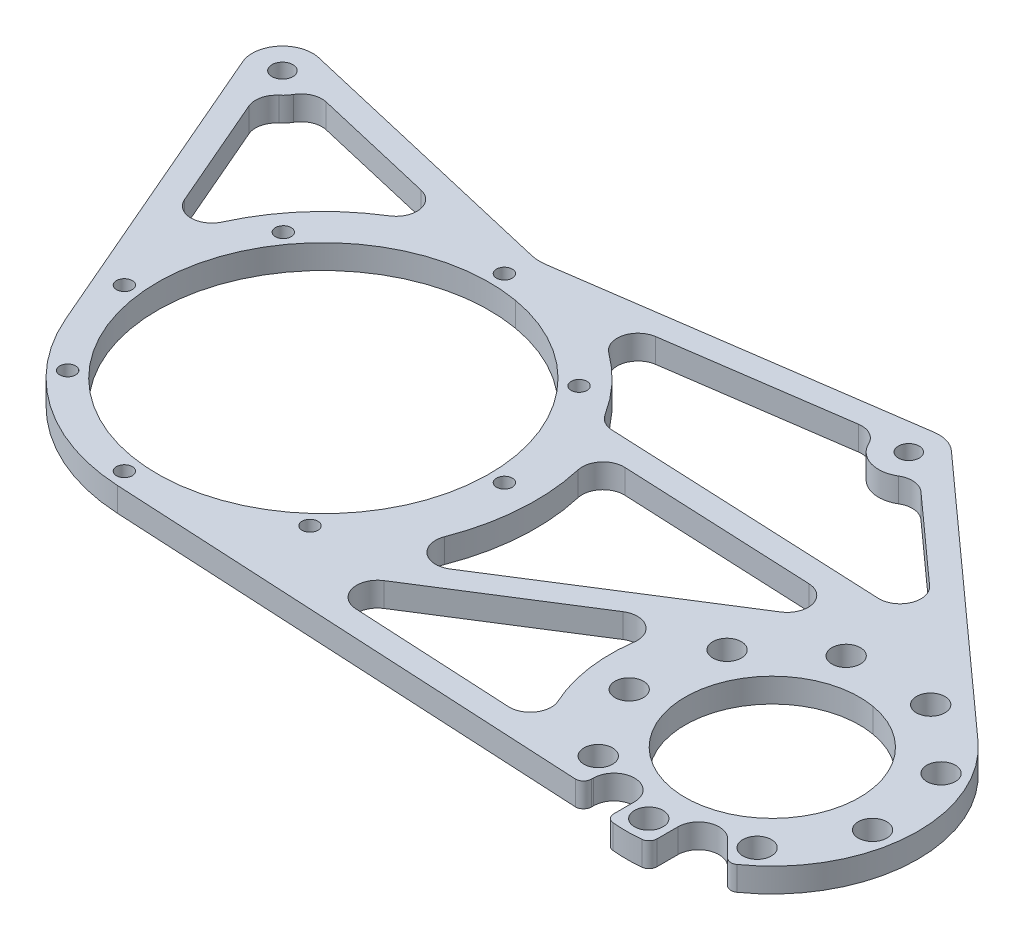
SolidWorks part; units mm, degrees
material "6061-T6 (SS)"
ref_plane "X-Y Datum" through (0, 0, 0) normal (0, 0, 1) x (1, 0, 0)
ref_plane "X-Z Datum" through (0, 0, 0) normal (0, 1, 0) x (1, 0, 0)
ref_plane "Y-Z Datum" through (0, 0, 0) normal (1, 0, 0) x (0, 0, -1)
sketch "Sketch2" plane through (0, 31.3819, 0) normal (0, 1, 0) x (1, 0, 0)
  line L0 (-693.7583, -176.702) -> (-693.7583, -183.2747) construction
  line L1 (-680.0808, -183.2747) -> (-680.0808, -176.702) construction
  line L2 (-668.9846, -172.1058) -> (-663.7197, -177.3707) construction
  line L3 (-693.7583, -176.702) -> (-693.7583, -183.2747)
  line L4 (-680.0808, -183.2747) -> (-680.0808, -176.702)
  line L5 (-668.9846, -172.1058) -> (-663.7197, -177.3707)
  line L6 (-966.641, -0.354) -> (-738.041, -0.354)
  line L7 (-727.7656, -5.5904) -> (-649.7224, -113.0358)
  line L9 (-977.8288, -19.0644) -> (-913.2312, -139.3061)
  line L10 (-706.7583, -177.279) -> (-706.7583, -176.702) construction
  line L11 (-706.7583, -177.279) -> (-706.7583, -176.702)
  line L12 (-861.9259, -171.8334) -> (-709.2983, -179.819)
  line L13 (-858.691, -110.0055) -> (-686.9195, -140.054) construction
  line L14 (-972.26, -24.9963) -> (-955.4664, -39.59) construction
  line L15 (-941.4162, -26.937) -> (-954.1775, -8.712) construction
  line L16 (-751.1929, -14.159) -> (-755.4346, -35.9995) construction
  line L17 (-737.4517, -41.8408) -> (-728.049, -21.6768) construction
  line L18 (-972.26, -24.9963) -> (-955.4664, -39.59)
  line L19 (-941.4162, -26.937) -> (-954.1775, -8.712)
  line L20 (-751.1929, -14.159) -> (-755.4346, -35.9995)
  line L21 (-737.4517, -41.8408) -> (-728.049, -21.6768)
  line L22 (-949.2186, -22.8753) -> (-746.0843, -28.2904)
  line L23 (-739.7146, -30.7335) -> (-656.1751, -105.8723)
  line L24 (-957.9647, -36.1729) -> (-915.5404, -134.527)
  arc A0 (-710.607, -179.4559) -> (-706.7583, -177.279) centre (-709.2983, -177.279) ccw construction
  arc A1 (-693.7583, -176.702) -> (-706.7583, -176.702) centre (-700.2583, -176.702) ccw construction
  arc A2 (-693.7583, -183.2747) -> (-691.4697, -185.8023) centre (-691.2183, -183.2747) ccw construction
  arc A3 (-691.4697, -185.8023) -> (-682.3694, -185.8023) centre (-686.9195, -140.054) ccw construction
  arc A4 (-682.3694, -185.8023) -> (-680.0808, -183.2747) centre (-682.6208, -183.2747) ccw construction
  arc A5 (-668.9846, -172.1058) -> (-680.0808, -176.702) centre (-673.5808, -176.702) ccw construction
  arc A6 (-663.7197, -177.3707) -> (-660.4619, -177.6519) centre (-661.9236, -175.5746) ccw construction
  arc A7 (-660.4619, -177.6519) -> (-710.607, -179.4559) centre (-686.9195, -140.054) ccw construction
  circle A8 centre (-858.691, -110.0055) radius 52.3875 construction
  circle A9 centre (-858.691, -110.0055) radius 61.9125 construction
  circle A10 centre (-738.041, -13.054) radius 12.7 construction
  circle A11 centre (-966.641, -13.054) radius 12.7 construction
  arc A12 (-710.607, -179.4559) -> (-706.7583, -177.279) centre (-709.2983, -177.279) ccw
  arc A13 (-693.7583, -176.702) -> (-706.7583, -176.702) centre (-700.2583, -176.702) ccw
  arc A14 (-693.7583, -183.2747) -> (-691.4697, -185.8023) centre (-691.2183, -183.2747) ccw
  arc A15 (-691.4697, -185.8023) -> (-682.3694, -185.8023) centre (-686.9195, -140.054) ccw
  arc A16 (-682.3694, -185.8023) -> (-680.0808, -183.2747) centre (-682.6208, -183.2747) ccw
  arc A17 (-668.9846, -172.1058) -> (-680.0808, -176.702) centre (-673.5808, -176.702) ccw
  arc A18 (-663.7197, -177.3707) -> (-660.4619, -177.6519) centre (-661.9236, -175.5746) ccw
  arc A19 (-660.4619, -177.6519) -> (-710.607, -179.4559) centre (-686.9195, -140.054) ccw
  circle A20 centre (-858.691, -110.0055) radius 52.3875
  circle A21 centre (-858.691, -110.0055) radius 61.9125
  circle A22 centre (-738.041, -13.054) radius 12.7
  circle A23 centre (-966.641, -13.054) radius 12.7
  circle A24 centre (-901.1618, -148.2463) radius 2.5 construction
  circle A25 centre (-915.528, -115.9793) radius 2.5 construction
  circle A26 centre (-904.9264, -76.4135) radius 2.5 construction
  circle A27 centre (-858.691, -52.8555) radius 2.5 construction
  circle A28 centre (-816.2203, -71.7646) radius 2.5 construction
  circle A29 centre (-801.541, -110.0055) radius 2.5 construction
  circle A30 centre (-820.4502, -152.4762) radius 2.5 construction
  circle A31 centre (-864.6648, -166.8424) radius 2.5 construction
  circle A32 centre (-901.1618, -148.2463) radius 2.5
  circle A33 centre (-915.528, -115.9793) radius 2.5
  circle A34 centre (-904.9264, -76.4135) radius 2.5
  circle A35 centre (-858.691, -52.8555) radius 2.5
  circle A36 centre (-816.2203, -71.7646) radius 2.5
  circle A37 centre (-801.541, -110.0055) radius 2.5
  circle A38 centre (-820.4502, -152.4762) radius 2.5
  circle A39 centre (-864.6648, -166.8424) radius 2.5
  circle A40 centre (-686.9195, -140.054) radius 27.4955 construction
  circle A41 centre (-686.9195, -140.054) radius 27.4955
  circle A42 centre (-711.9883, -169.9297) radius 4.5 construction
  circle A43 centre (-725.3271, -146.8263) radius 4.5 construction
  circle A44 centre (-720.6945, -120.554) radius 4.5 construction
  circle A45 centre (-700.2583, -103.406) radius 4.5 construction
  circle A46 centre (-673.5808, -103.406) radius 4.5 construction
  circle A47 centre (-653.1446, -120.554) radius 4.5 construction
  circle A48 centre (-648.512, -146.8263) radius 4.5 construction
  circle A49 centre (-661.8508, -169.9297) radius 4.5 construction
  circle A50 centre (-686.9195, -179.054) radius 4.5 construction
  circle A51 centre (-711.9883, -169.9297) radius 4.5
  circle A52 centre (-725.3271, -146.8263) radius 4.5
  circle A53 centre (-720.6945, -120.554) radius 4.5
  circle A54 centre (-700.2583, -103.406) radius 4.5
  circle A55 centre (-673.5808, -103.406) radius 4.5
  circle A56 centre (-653.1446, -120.554) radius 4.5
  circle A57 centre (-648.512, -146.8263) radius 4.5
  circle A58 centre (-661.8508, -169.9297) radius 4.5
  circle A59 centre (-686.9195, -179.054) radius 4.5
  circle A60 centre (-966.641, -13.054) radius 3.3
  circle A61 centre (-738.041, -13.054) radius 3.3
  arc A62 (-955.4664, -39.59) -> (-941.4162, -26.937) centre (-949.2186, -32.4003) ccw construction
  arc A63 (-749.3237, -37.1863) -> (-742.8448, -38.4445) centre (-746.0843, -37.8154) ccw construction
  arc A64 (-742.8448, -38.4445) -> (-749.3237, -37.1863) centre (-746.0843, -37.8154) ccw construction
  arc A65 (-755.4346, -35.9995) -> (-737.4517, -41.8408) centre (-746.0843, -37.8154) ccw construction
  arc A66 (-955.4664, -39.59) -> (-941.4162, -26.937) centre (-949.2186, -32.4003) ccw
  arc A67 (-749.3237, -37.1863) -> (-742.8448, -38.4445) centre (-746.0843, -37.8154) ccw
  arc A68 (-742.8448, -38.4445) -> (-749.3237, -37.1863) centre (-746.0843, -37.8154) ccw
  arc A69 (-755.4346, -35.9995) -> (-737.4517, -41.8408) centre (-746.0843, -37.8154) ccw
  circle A70 centre (-949.2186, -32.4003) radius 3.3
  circle A71 centre (-949.2186, -32.4003) radius 9.525
  circle A72 centre (-746.0843, -37.8154) radius 9.525
  point P94 (-949.2186, -32.4003)
  dimension "D1" = 6.6
  dimension "D2" = 6.6
  dimension "D3" = 6.6
extrude "Boss-Extrude1" add sketch "Sketch2" along normal blind 7.62 contours A21 A39 A38 A37 A36 A35 A34 A33 A32 A20 | A18 A19 A12 L11 A13 L3 A14 A15 A16 L4 A17 L5 A59 A58 A57 A56 A55 A54 A53 A52 A51 A41 | L13 A21 L12 A12 A19 | A21 L13 A19 L23 L21 A69 L20 L22 L19 A66 L18 L24 | A69 A72 A68 A67 | A72 L22 L20 | A72 L21 L23 | A71 L24 L18 | A71 L19 L22 | A71 A66 L22 A70 region at (-700.2583, 31.3819, 168.9016) region at (-773.051, 31.3819, 154.3682) region at (-890.9045, 31.3819, 160.8157) region at (-806.8861, 31.3819, 67.2042) region at (-956.9478, 31.3819, 38.0512) region at (-736.2382, 31.3819, 35.8095) region at (-956.6903, 31.3819, 37.8629) region at (-748.9437, 31.3819, 46.6182) region at (-752.4763, 31.3819, 29.8585) region at (-944.5842, 31.3819, 23.8004)
sketch "Sketch3" plane through (0, 31.3819, 0) normal (0, -1, 0) x (1, 0, 0)
  line L1 (-949.2186, 22.8753) -> (-746.0843, 28.2904) construction
  line L5 (-861.9259, 171.8334) -> (-709.2983, 179.819) construction
  line L6 (-977.8288, 19.0644) -> (-913.2312, 139.3061) construction
  line L7 (-727.7656, 5.5904) -> (-649.7224, 113.0358) construction
  line L13 (-751.1929, 14.159) -> (-755.4346, 35.9995) construction
  line L16 (-966.641, 0.354) -> (-738.041, 0.354) construction
  line L19 (-663.7197, 177.3707) -> (-668.9846, 172.1058)
  line L20 (-680.0808, 176.702) -> (-680.0808, 183.2747)
  line L21 (-693.7583, 183.2747) -> (-693.7583, 176.702)
  line L22 (-706.7583, 176.702) -> (-706.7583, 177.279)
  line L23 (-663.7197, 177.3707) -> (-668.9846, 172.1058)
  line L24 (-680.0808, 176.702) -> (-680.0808, 183.2747)
  line L25 (-693.7583, 183.2747) -> (-693.7583, 176.702)
  line L26 (-706.7583, 176.702) -> (-706.7583, 177.279)
  line L28 (-861.9259, 171.8334) -> (-709.2983, 179.819)
  line L29 (-977.8288, 19.0644) -> (-913.2312, 139.3061)
  line L30 (-727.7656, 5.5904) -> (-649.7224, 113.0358)
  line L31 (-966.641, 0.354) -> (-738.041, 0.354)
  line L34 (-737.4517, 41.8408) -> (-728.049, 21.6768) construction
  line L35 (-972.26, 24.9963) -> (-955.4664, 39.59) construction
  line L36 (-947.0539, 23.1246) -> (-856.9722, 44.1471)
  line L37 (-856.9722, 44.1471) -> (-747.4408, 28.3875)
  line L44 (-941.4162, 26.937) -> (-954.1775, 8.712) construction
  line L45 (-957.9647, 36.1729) -> (-915.5404, 134.527) construction
  line L46 (-739.7146, 30.7335) -> (-656.1751, 105.8723) construction
  line L47 (-861.9259, 171.8334) -> (-709.2983, 179.819)
  line L48 (-977.8288, 19.0644) -> (-913.2312, 139.3061)
  line L49 (-727.7656, 5.5904) -> (-649.7224, 113.0358)
  line L50 (-966.641, 0.354) -> (-738.041, 0.354)
  line L51 (-949.2186, 22.8753) -> (-746.0843, 28.2904)
  line L52 (-751.1929, 14.159) -> (-755.4346, 35.9995)
  line L53 (-737.4517, 41.8408) -> (-728.049, 21.6768)
  line L54 (-972.26, 24.9963) -> (-955.4664, 39.59)
  line L55 (-941.4162, 26.937) -> (-954.1775, 8.712)
  line L56 (-957.9647, 36.1729) -> (-915.5404, 134.527)
  line L57 (-739.7146, 30.7335) -> (-656.1751, 105.8723)
  arc A1 (-737.4517, 41.8408) -> (-755.4346, 35.9995) centre (-746.0843, 37.8154) ccw construction
  circle A3 centre (-966.641, 13.054) radius 12.7
  circle A5 centre (-966.641, 13.054) radius 12.7
  circle A7 centre (-738.041, 13.054) radius 12.7
  circle A9 centre (-738.041, 13.054) radius 12.7
  circle A11 centre (-858.691, 110.0055) radius 61.9125
  circle A13 centre (-858.691, 110.0055) radius 61.9125
  circle A15 centre (-858.691, 110.0055) radius 52.3875
  circle A17 centre (-858.691, 110.0055) radius 52.3875
  circle A19 centre (-686.9195, 140.054) radius 27.4955
  circle A21 centre (-686.9195, 140.054) radius 27.4955
  circle A23 centre (-864.6648, 166.8424) radius 2.5
  circle A25 centre (-864.6648, 166.8424) radius 2.5
  circle A27 centre (-820.4502, 152.4762) radius 2.5
  circle A29 centre (-820.4502, 152.4762) radius 2.5
  circle A31 centre (-801.541, 110.0055) radius 2.5
  circle A33 centre (-801.541, 110.0055) radius 2.5
  circle A35 centre (-816.2203, 71.7646) radius 2.5
  circle A37 centre (-816.2203, 71.7646) radius 2.5
  circle A39 centre (-858.691, 52.8555) radius 2.5
  circle A41 centre (-858.691, 52.8555) radius 2.5
  circle A43 centre (-904.9264, 76.4135) radius 2.5
  circle A46 centre (-904.9264, 76.4135) radius 2.5
  circle A47 centre (-915.528, 115.9793) radius 2.5
  circle A48 centre (-915.528, 115.9793) radius 2.5
  circle A49 centre (-901.1618, 148.2463) radius 2.5
  circle A50 centre (-901.1618, 148.2463) radius 2.5
  circle A51 centre (-720.6945, 120.554) radius 4.5
  circle A52 centre (-720.6945, 120.554) radius 4.5
  circle A68 centre (-725.3271, 146.8263) radius 4.5
  circle A69 centre (-725.3271, 146.8263) radius 4.5
  circle A70 centre (-711.9883, 169.9297) radius 4.5
  circle A71 centre (-711.9883, 169.9297) radius 4.5
  circle A72 centre (-738.041, 13.054) radius 3.3
  circle A73 centre (-738.041, 13.054) radius 3.3
  circle A74 centre (-966.641, 13.054) radius 3.3
  circle A75 centre (-966.641, 13.054) radius 3.3
  circle A76 centre (-686.9195, 179.054) radius 4.5
  circle A77 centre (-686.9195, 179.054) radius 4.5
  circle A78 centre (-661.8508, 169.9297) radius 4.5
  circle A79 centre (-661.8508, 169.9297) radius 4.5
  circle A80 centre (-648.512, 146.8263) radius 4.5
  circle A81 centre (-648.512, 146.8263) radius 4.5
  circle A82 centre (-653.1446, 120.554) radius 4.5
  circle A83 centre (-653.1446, 120.554) radius 4.5
  circle A84 centre (-673.5808, 103.406) radius 4.5
  circle A85 centre (-673.5808, 103.406) radius 4.5
  circle A86 centre (-700.2583, 103.406) radius 4.5
  circle A87 centre (-700.2583, 103.406) radius 4.5
  arc A95 (-710.607, 179.4559) -> (-660.4619, 177.6519) centre (-686.9195, 140.054) ccw
  arc A96 (-660.4619, 177.6519) -> (-663.7197, 177.3707) centre (-661.9236, 175.5746) ccw
  arc A97 (-680.0808, 176.702) -> (-668.9846, 172.1058) centre (-673.5808, 176.702) ccw
  arc A98 (-680.0808, 183.2747) -> (-682.3694, 185.8023) centre (-682.6208, 183.2747) ccw
  arc A99 (-682.3694, 185.8023) -> (-691.4697, 185.8023) centre (-686.9195, 140.054) ccw
  arc A100 (-691.4697, 185.8023) -> (-693.7583, 183.2747) centre (-691.2183, 183.2747) ccw
  arc A101 (-706.7583, 176.702) -> (-693.7583, 176.702) centre (-700.2583, 176.702) ccw
  arc A102 (-706.7583, 177.279) -> (-710.607, 179.4559) centre (-709.2983, 177.279) ccw
  arc A103 (-710.607, 179.4559) -> (-660.4619, 177.6519) centre (-686.9195, 140.054) ccw
  arc A104 (-660.4619, 177.6519) -> (-663.7197, 177.3707) centre (-661.9236, 175.5746) ccw
  arc A105 (-680.0808, 176.702) -> (-668.9846, 172.1058) centre (-673.5808, 176.702) ccw
  arc A106 (-680.0808, 183.2747) -> (-682.3694, 185.8023) centre (-682.6208, 183.2747) ccw
  arc A107 (-682.3694, 185.8023) -> (-691.4697, 185.8023) centre (-686.9195, 140.054) ccw
  arc A108 (-691.4697, 185.8023) -> (-693.7583, 183.2747) centre (-691.2183, 183.2747) ccw
  arc A109 (-706.7583, 176.702) -> (-693.7583, 176.702) centre (-700.2583, 176.702) ccw
  arc A110 (-706.7583, 177.279) -> (-710.607, 179.4559) centre (-709.2983, 177.279) ccw
  circle A152 centre (-746.0843, 37.8154) radius 9.525
  circle A153 centre (-746.0843, 37.8154) radius 9.525
  circle A154 centre (-949.2186, 32.4003) radius 9.525
  circle A155 centre (-949.2186, 32.4003) radius 9.525
  circle A156 centre (-949.2186, 32.4003) radius 3.3
  circle A157 centre (-949.2186, 32.4003) radius 3.3
  arc A158 (-941.4162, 26.937) -> (-955.4664, 39.59) centre (-949.2186, 32.4003) ccw construction
  arc A159 (-742.8448, 38.4445) -> (-749.3237, 37.1863) centre (-746.0843, 37.8154) ccw
  arc A160 (-749.3237, 37.1863) -> (-742.8448, 38.4445) centre (-746.0843, 37.8154) ccw
  arc A161 (-742.8448, 38.4445) -> (-749.3237, 37.1863) centre (-746.0843, 37.8154) ccw
  arc A162 (-749.3237, 37.1863) -> (-742.8448, 38.4445) centre (-746.0843, 37.8154) ccw
  arc A163 (-737.4517, 41.8408) -> (-755.4346, 35.9995) centre (-746.0843, 37.8154) ccw
  arc A164 (-941.4162, 26.937) -> (-955.4664, 39.59) centre (-949.2186, 32.4003) ccw
  dimension "D24" = 0
  dimension "D25" = 0
  dimension "D26" = 90.0818
  dimension "D27" = 21.0225
  dimension "D1" = 0
  dimension "D2" = 0
  dimension "D3" = 0
  dimension "D4" = 0
  dimension "D5" = 0
  dimension "D6" = 0
  dimension "D7" = 0
  dimension "D8" = 0
  dimension "D9" = 0
  dimension "D10" = 0
  dimension "D11" = 0
  dimension "D12" = 0
  dimension "D13" = 0
  dimension "D14" = 0
  dimension "D15" = 0
  dimension "D16" = 0
  dimension "D17" = 0
  dimension "D18" = 0
  dimension "D19" = 0
  dimension "D20" = 0
  dimension "D21" = 0
  dimension "D22" = 0
  dimension "D23" = 0
  dimension "D52" = 0
  dimension "D53" = 0
  dimension "D54" = 0
  dimension "D55" = 0
ref_point "Point1"
ref_point "Point2"
ref_plane "Plane1" through (-858.691, 31.3819, 110.0055) normal (0.985, 0, 0.1723) x (0.1723, 0, -0.985)
ref_plane "Plane2" through (-686.9195, 31.3819, 140.054) normal (-0.985, 0, -0.1723) x (-0.1723, 0, 0.985)
split line "Split Line1"
split line "Split Line2"
ref_axis "Axis1" through (-858.691, 39.0019, 110.0055) along (0, -1, 0)
ref_axis "Axis2" through (-686.9195, 39.0019, 140.054) along (0, -1, 0)
extrude "Cut-Extrude1" cut sketch "Sketch3" against normal through all contours L36 L55 L51 L52 L37 | A155 L51 L55 L36 | A153 L37 L52 L51 region at (-751.5495, 31.3819, 28.5688) region at (-850.6911, 31.3819, 31.7926) region at (-945.2616, 31.3819, 23.2848)
fillet "Fillet2" radius 12.7 1 edges at (-856.9722, 35.1919, 44.1471)
sketch "Sketch4" plane through (0, 31.3819, 0) normal (0, -1, 0) x (1, 0, 0)
  line L0 (-861.9259, 171.8334) -> (-709.2983, 179.819) construction
  line L1 (-727.7656, 5.5904) -> (-649.7224, 113.0358) construction
  line L2 (-977.8288, 19.0644) -> (-913.2312, 139.3061) construction
  line L4 (-706.7583, 176.702) -> (-706.7583, 177.279)
  line L5 (-663.7197, 177.3707) -> (-668.9846, 172.1058)
  line L6 (-680.0808, 176.702) -> (-680.0808, 183.2747)
  line L7 (-693.7583, 183.2747) -> (-693.7583, 176.702)
  line L8 (-706.7583, 176.702) -> (-706.7583, 177.279)
  line L9 (-663.7197, 177.3707) -> (-668.9846, 172.1058)
  line L10 (-680.0808, 176.702) -> (-680.0808, 183.2747)
  line L11 (-693.7583, 183.2747) -> (-693.7583, 176.702)
  line L13 (-966.641, 0.354) -> (-738.041, 0.354) construction
  line L14 (-861.9259, 171.8334) -> (-709.2983, 179.819)
  line L15 (-727.7656, 5.5904) -> (-649.7224, 113.0358)
  line L16 (-977.8288, 19.0644) -> (-913.2312, 139.3061)
  line L17 (-861.9259, 171.8334) -> (-709.2983, 179.819) construction
  line L19 (-966.641, 0.354) -> (-738.041, 0.354)
  line L20 (-922.3006, 99.6155) -> (-952.4637, 29.6868)
  line L21 (-952.4637, 29.6868) -> (-875.2298, 47.711)
  line L22 (-727.338, 171.2447) -> (-811.2904, 166.8523)
  line L23 (-811.2904, 166.8523) -> (-732.4764, 117.0088)
  line L24 (-812.7344, 158.7495) -> (-704.8294, 90.5083)
  line L25 (-704.8294, 90.5083) -> (-795.9976, 86.3933)
  line L26 (-837.6883, 49.071) -> (-755.593, 37.2589)
  line L27 (-802.4787, 78.4731) -> (-692.5141, 83.4364)
  line L28 (-692.5141, 83.4364) -> (-737.8716, 42.64)
  line L29 (-977.8288, 19.0644) -> (-913.2312, 139.3061) construction
  line L30 (-727.7656, 5.5904) -> (-649.7224, 113.0358) construction
  line L31 (-966.641, 0.354) -> (-738.041, 0.354) construction
  line L32 (-663.7197, 177.3707) -> (-668.9846, 172.1058)
  line L33 (-680.0808, 176.702) -> (-680.0808, 183.2747)
  line L34 (-693.7583, 183.2747) -> (-693.7583, 176.702)
  line L35 (-706.7583, 176.702) -> (-706.7583, 177.279)
  line L36 (-663.7197, 177.3707) -> (-668.9846, 172.1058)
  line L37 (-680.0808, 176.702) -> (-680.0808, 183.2747)
  line L38 (-693.7583, 183.2747) -> (-693.7583, 176.702)
  line L39 (-706.7583, 176.702) -> (-706.7583, 177.279)
  line L40 (-949.2186, 22.8753) -> (-746.0843, 28.2904) construction
  line L41 (-751.1929, 14.159) -> (-755.4346, 35.9995) construction
  line L42 (-737.4517, 41.8408) -> (-728.049, 21.6768) construction
  line L43 (-972.26, 24.9963) -> (-955.4664, 39.59) construction
  line L44 (-941.4162, 26.937) -> (-954.1775, 8.712) construction
  line L45 (-957.9647, 36.1729) -> (-915.5404, 134.527) construction
  line L46 (-739.7146, 30.7335) -> (-656.1751, 105.8723) construction
  line L47 (-861.9259, 171.8334) -> (-709.2983, 179.819)
  line L48 (-977.8288, 19.0644) -> (-913.2312, 139.3061)
  line L49 (-727.7656, 5.5904) -> (-649.7224, 113.0358)
  line L50 (-966.641, 0.354) -> (-738.041, 0.354)
  line L51 (-949.2186, 22.8753) -> (-746.0843, 28.2904)
  line L52 (-751.1929, 14.159) -> (-755.4346, 35.9995)
  line L53 (-737.4517, 41.8408) -> (-728.049, 21.6768)
  line L54 (-972.26, 24.9963) -> (-955.4664, 39.59)
  line L55 (-941.4162, 26.937) -> (-954.1775, 8.712)
  line L56 (-957.9647, 36.1729) -> (-915.5404, 134.527)
  line L57 (-739.7146, 30.7335) -> (-656.1751, 105.8723)
  line L58 (-947.0539, 23.1246) -> (-859.3005, 43.6037) construction
  line L60 (-854.6056, 43.8066) -> (-747.4408, 28.3875) construction
  circle A1 centre (-858.691, 110.0055) radius 52.3875
  circle A2 centre (-858.691, 110.0055) radius 52.3875
  circle A3 centre (-858.691, 110.0055) radius 61.9125
  circle A4 centre (-858.691, 110.0055) radius 61.9125
  circle A5 centre (-738.041, 13.054) radius 12.7
  circle A6 centre (-738.041, 13.054) radius 12.7
  circle A7 centre (-966.641, 13.054) radius 12.7
  circle A8 centre (-966.641, 13.054) radius 12.7
  circle A9 centre (-858.691, 52.8555) radius 2.5
  circle A10 centre (-858.691, 52.8555) radius 2.5
  circle A11 centre (-816.2203, 71.7646) radius 2.5
  circle A12 centre (-816.2203, 71.7646) radius 2.5
  circle A13 centre (-801.541, 110.0055) radius 2.5
  circle A14 centre (-801.541, 110.0055) radius 2.5
  circle A15 centre (-820.4502, 152.4762) radius 2.5
  circle A16 centre (-820.4502, 152.4762) radius 2.5
  circle A17 centre (-864.6648, 166.8424) radius 2.5
  circle A18 centre (-864.6648, 166.8424) radius 2.5
  circle A19 centre (-686.9195, 140.054) radius 27.4955
  circle A20 centre (-686.9195, 140.054) radius 27.4955
  circle A21 centre (-725.3271, 146.8263) radius 4.5
  circle A22 centre (-725.3271, 146.8263) radius 4.5
  circle A23 centre (-720.6945, 120.554) radius 4.5
  circle A24 centre (-720.6945, 120.554) radius 4.5
  circle A25 centre (-901.1618, 148.2463) radius 2.5
  circle A26 centre (-901.1618, 148.2463) radius 2.5
  circle A27 centre (-915.528, 115.9793) radius 2.5
  circle A28 centre (-915.528, 115.9793) radius 2.5
  circle A29 centre (-904.9264, 76.4135) radius 2.5
  circle A30 centre (-904.9264, 76.4135) radius 2.5
  circle A31 centre (-661.8508, 169.9297) radius 4.5
  circle A32 centre (-661.8508, 169.9297) radius 4.5
  circle A33 centre (-686.9195, 179.054) radius 4.5
  circle A34 centre (-686.9195, 179.054) radius 4.5
  circle A35 centre (-966.641, 13.054) radius 3.3
  circle A36 centre (-966.641, 13.054) radius 3.3
  circle A37 centre (-738.041, 13.054) radius 3.3
  circle A38 centre (-738.041, 13.054) radius 3.3
  circle A39 centre (-711.9883, 169.9297) radius 4.5
  circle A40 centre (-711.9883, 169.9297) radius 4.5
  circle A41 centre (-700.2583, 103.406) radius 4.5
  circle A42 centre (-700.2583, 103.406) radius 4.5
  circle A43 centre (-673.5808, 103.406) radius 4.5
  circle A44 centre (-673.5808, 103.406) radius 4.5
  circle A45 centre (-653.1446, 120.554) radius 4.5
  circle A46 centre (-653.1446, 120.554) radius 4.5
  circle A47 centre (-648.512, 146.8263) radius 4.5
  circle A48 centre (-648.512, 146.8263) radius 4.5
  arc A49 (-875.2298, 47.711) -> (-922.3006, 99.6155) centre (-858.691, 110.0055) cw
  arc A50 (-727.338, 171.2447) -> (-732.4764, 117.0088) centre (-686.9195, 140.054) ccw
  arc A51 (-812.7344, 158.7495) -> (-795.9976, 86.3933) centre (-858.691, 110.0055) cw
  arc A52 (-837.6883, 49.071) -> (-802.4787, 78.4731) centre (-858.691, 110.0055) ccw
  arc A53 (-737.4517, 41.8408) -> (-755.4346, 35.9995) centre (-746.0843, 37.8154) ccw construction
  circle A54 centre (-966.641, 13.054) radius 12.7
  circle A55 centre (-966.641, 13.054) radius 12.7
  arc A56 (-706.7583, 177.279) -> (-710.607, 179.4559) centre (-709.2983, 177.279) ccw
  arc A57 (-710.607, 179.4559) -> (-660.4619, 177.6519) centre (-686.9195, 140.054) ccw
  arc A58 (-660.4619, 177.6519) -> (-663.7197, 177.3707) centre (-661.9236, 175.5746) ccw
  arc A59 (-680.0808, 176.702) -> (-668.9846, 172.1058) centre (-673.5808, 176.702) ccw
  arc A60 (-680.0808, 183.2747) -> (-682.3694, 185.8023) centre (-682.6208, 183.2747) ccw
  arc A61 (-682.3694, 185.8023) -> (-691.4697, 185.8023) centre (-686.9195, 140.054) ccw
  arc A62 (-691.4697, 185.8023) -> (-693.7583, 183.2747) centre (-691.2183, 183.2747) ccw
  arc A63 (-706.7583, 176.702) -> (-693.7583, 176.702) centre (-700.2583, 176.702) ccw
  arc A64 (-706.7583, 177.279) -> (-710.607, 179.4559) centre (-709.2983, 177.279) ccw
  arc A65 (-710.607, 179.4559) -> (-660.4619, 177.6519) centre (-686.9195, 140.054) ccw
  arc A66 (-660.4619, 177.6519) -> (-663.7197, 177.3707) centre (-661.9236, 175.5746) ccw
  arc A67 (-680.0808, 176.702) -> (-668.9846, 172.1058) centre (-673.5808, 176.702) ccw
  arc A68 (-680.0808, 183.2747) -> (-682.3694, 185.8023) centre (-682.6208, 183.2747) ccw
  arc A69 (-682.3694, 185.8023) -> (-691.4697, 185.8023) centre (-686.9195, 140.054) ccw
  arc A70 (-691.4697, 185.8023) -> (-693.7583, 183.2747) centre (-691.2183, 183.2747) ccw
  arc A71 (-706.7583, 176.702) -> (-693.7583, 176.702) centre (-700.2583, 176.702) ccw
  circle A72 centre (-738.041, 13.054) radius 12.7
  circle A73 centre (-738.041, 13.054) radius 12.7
  circle A74 centre (-858.691, 110.0055) radius 61.9125
  circle A75 centre (-858.691, 110.0055) radius 61.9125
  circle A76 centre (-858.691, 110.0055) radius 52.3875
  circle A77 centre (-858.691, 110.0055) radius 52.3875
  circle A78 centre (-686.9195, 140.054) radius 27.4955
  circle A79 centre (-686.9195, 140.054) radius 27.4955
  circle A80 centre (-864.6648, 166.8424) radius 2.5
  circle A81 centre (-864.6648, 166.8424) radius 2.5
  circle A82 centre (-820.4502, 152.4762) radius 2.5
  circle A83 centre (-820.4502, 152.4762) radius 2.5
  circle A84 centre (-801.541, 110.0055) radius 2.5
  circle A85 centre (-801.541, 110.0055) radius 2.5
  circle A86 centre (-816.2203, 71.7646) radius 2.5
  circle A87 centre (-816.2203, 71.7646) radius 2.5
  circle A88 centre (-858.691, 52.8555) radius 2.5
  circle A89 centre (-858.691, 52.8555) radius 2.5
  circle A90 centre (-904.9264, 76.4135) radius 2.5
  circle A91 centre (-904.9264, 76.4135) radius 2.5
  circle A92 centre (-915.528, 115.9793) radius 2.5
  circle A93 centre (-915.528, 115.9793) radius 2.5
  circle A94 centre (-901.1618, 148.2463) radius 2.5
  circle A95 centre (-901.1618, 148.2463) radius 2.5
  circle A96 centre (-720.6945, 120.554) radius 4.5
  circle A97 centre (-720.6945, 120.554) radius 4.5
  circle A98 centre (-725.3271, 146.8263) radius 4.5
  circle A99 centre (-725.3271, 146.8263) radius 4.5
  circle A100 centre (-711.9883, 169.9297) radius 4.5
  circle A101 centre (-711.9883, 169.9297) radius 4.5
  circle A102 centre (-738.041, 13.054) radius 3.3
  circle A103 centre (-738.041, 13.054) radius 3.3
  circle A104 centre (-966.641, 13.054) radius 3.3
  circle A105 centre (-966.641, 13.054) radius 3.3
  circle A106 centre (-686.9195, 179.054) radius 4.5
  circle A107 centre (-686.9195, 179.054) radius 4.5
  circle A108 centre (-661.8508, 169.9297) radius 4.5
  circle A109 centre (-661.8508, 169.9297) radius 4.5
  circle A110 centre (-648.512, 146.8263) radius 4.5
  circle A111 centre (-648.512, 146.8263) radius 4.5
  circle A112 centre (-653.1446, 120.554) radius 4.5
  circle A113 centre (-653.1446, 120.554) radius 4.5
  circle A114 centre (-673.5808, 103.406) radius 4.5
  circle A115 centre (-673.5808, 103.406) radius 4.5
  circle A116 centre (-700.2583, 103.406) radius 4.5
  circle A117 centre (-700.2583, 103.406) radius 4.5
  circle A118 centre (-746.0843, 37.8154) radius 9.525
  circle A119 centre (-746.0843, 37.8154) radius 9.525
  circle A120 centre (-949.2186, 32.4003) radius 9.525
  circle A121 centre (-949.2186, 32.4003) radius 9.525
  circle A122 centre (-949.2186, 32.4003) radius 3.3
  circle A123 centre (-949.2186, 32.4003) radius 3.3
  arc A124 (-941.4162, 26.937) -> (-955.4664, 39.59) centre (-949.2186, 32.4003) ccw construction
  arc A125 (-742.8448, 38.4445) -> (-749.3237, 37.1863) centre (-746.0843, 37.8154) ccw
  arc A126 (-749.3237, 37.1863) -> (-742.8448, 38.4445) centre (-746.0843, 37.8154) ccw
  arc A127 (-742.8448, 38.4445) -> (-749.3237, 37.1863) centre (-746.0843, 37.8154) ccw
  arc A128 (-749.3237, 37.1863) -> (-742.8448, 38.4445) centre (-746.0843, 37.8154) ccw
  arc A129 (-737.4517, 41.8408) -> (-755.4346, 35.9995) centre (-746.0843, 37.8154) ccw
  arc A130 (-941.4162, 26.937) -> (-955.4664, 39.59) centre (-949.2186, 32.4003) ccw
  arc A135 (-710.607, 179.4559) -> (-660.4619, 177.6519) centre (-686.9195, 140.054) ccw
  arc A136 (-660.4619, 177.6519) -> (-663.7197, 177.3707) centre (-661.9236, 175.5746) ccw
  arc A137 (-680.0808, 176.702) -> (-668.9846, 172.1058) centre (-673.5808, 176.702) ccw
  arc A138 (-680.0808, 183.2747) -> (-682.3694, 185.8023) centre (-682.6208, 183.2747) ccw
  arc A139 (-682.3694, 185.8023) -> (-691.4697, 185.8023) centre (-686.9195, 140.054) ccw
  arc A140 (-691.4697, 185.8023) -> (-693.7583, 183.2747) centre (-691.2183, 183.2747) ccw
  arc A141 (-706.7583, 176.702) -> (-693.7583, 176.702) centre (-700.2583, 176.702) ccw
  arc A142 (-706.7583, 177.279) -> (-710.607, 179.4559) centre (-709.2983, 177.279) ccw
  arc A143 (-710.607, 179.4559) -> (-660.4619, 177.6519) centre (-686.9195, 140.054) ccw
  arc A144 (-660.4619, 177.6519) -> (-663.7197, 177.3707) centre (-661.9236, 175.5746) ccw
  arc A145 (-680.0808, 176.702) -> (-668.9846, 172.1058) centre (-673.5808, 176.702) ccw
  arc A146 (-680.0808, 183.2747) -> (-682.3694, 185.8023) centre (-682.6208, 183.2747) ccw
  arc A147 (-682.3694, 185.8023) -> (-691.4697, 185.8023) centre (-686.9195, 140.054) ccw
  arc A148 (-691.4697, 185.8023) -> (-693.7583, 183.2747) centre (-691.2183, 183.2747) ccw
  arc A149 (-706.7583, 176.702) -> (-693.7583, 176.702) centre (-700.2583, 176.702) ccw
  arc A150 (-706.7583, 177.279) -> (-710.607, 179.4559) centre (-709.2983, 177.279) ccw
  dimension "D26" = 2.54
  dimension "D29" = 5.08
  dimension "D30" = 5.08
  dimension "D35" = 0
  dimension "D39" = 2.54
  dimension "D27" = 0
  dimension "D28" = 0
  dimension "D31" = 7.62
  dimension "D32" = 7.62
  dimension "D33" = 93.2524
  dimension "D34" = 49.8435
  dimension "D36" = 91.1683
  dimension "D38" = 7.62
  dimension "D40" = 7.62
  dimension "D67" = 7.62
  dimension "D68" = 7.62
  dimension "D69" = 7.62
  dimension "D1" = 0
  dimension "D2" = 0
  dimension "D3" = 0
  dimension "D4" = 0
  dimension "D5" = 0
  dimension "D6" = 0
  dimension "D7" = 0
  dimension "D8" = 0
  dimension "D9" = 0
  dimension "D10" = 0
  dimension "D11" = 0
  dimension "D12" = 0
  dimension "D13" = 0
  dimension "D14" = 0
  dimension "D15" = 0
  dimension "D16" = 0
  dimension "D17" = 0
  dimension "D18" = 0
  dimension "D19" = 0
  dimension "D20" = 0
  dimension "D21" = 0
  dimension "D22" = 0
  dimension "D23" = 0
  dimension "D24" = 0
  dimension "D25" = 0
  dimension "D41" = 0
  dimension "D42" = 0
  dimension "D43" = 0
  dimension "D44" = 0
  dimension "D45" = 0
  dimension "D46" = 0
  dimension "D47" = 0
  dimension "D48" = 0
  dimension "D49" = 0
  dimension "D50" = 0
  dimension "D51" = 0
  dimension "D52" = 0
  dimension "D53" = 0
  dimension "D54" = 0
  dimension "D55" = 0
  dimension "D56" = 0
  dimension "D57" = 0
  dimension "D58" = 0
  dimension "D59" = 0
  dimension "D60" = 0
  dimension "D61" = 0
  dimension "D62" = 0
  dimension "D63" = 0
  dimension "D64" = 0
  dimension "D65" = 0
  dimension "D66" = 0
extrude "Cut-Extrude2" cut sketch "Sketch4" against normal through all contours L21 A49 L20 A8 | A52 L26 A6 L28 L27 | L24 A51 L25 | A50 L22 L23 region at (-764.5478, 31.3819, 62.1346) region at (-919.2544, 31.3819, 56.9505) region at (-760.5637, 31.3819, 152.7731) region at (-765.2993, 31.3819, 109.4875)
fillet "Fillet3" radius 6.604 15 edges at (-732.4764, 35.1919, 117.0088) (-727.338, 35.1919, 171.2447) (-811.2904, 35.1919, 166.8523) (-704.8294, 35.1919, 90.5083) (-795.9976, 35.1919, 86.3933) (-812.7344, 35.1919, 158.7495) (-692.5141, 35.1919, 83.4364) (-802.4787, 35.1919, 78.4731) (-837.6883, 35.1919, 49.071) (-875.2298, 35.1919, 47.711) (-922.3006, 35.1919, 99.6155) (-737.8716, 35.1919, 42.64) (-755.593, 35.1919, 37.2589) (-939.6973, 35.1919, 32.6661) (-947.2715, 35.1919, 41.7242)
split line "Split Line3"
sketch "Sketch2<4>" plane through (0, 31.3819, 0) normal (0, 1, 0) x (1, 0, 0) same geometry as "Sketch2"
